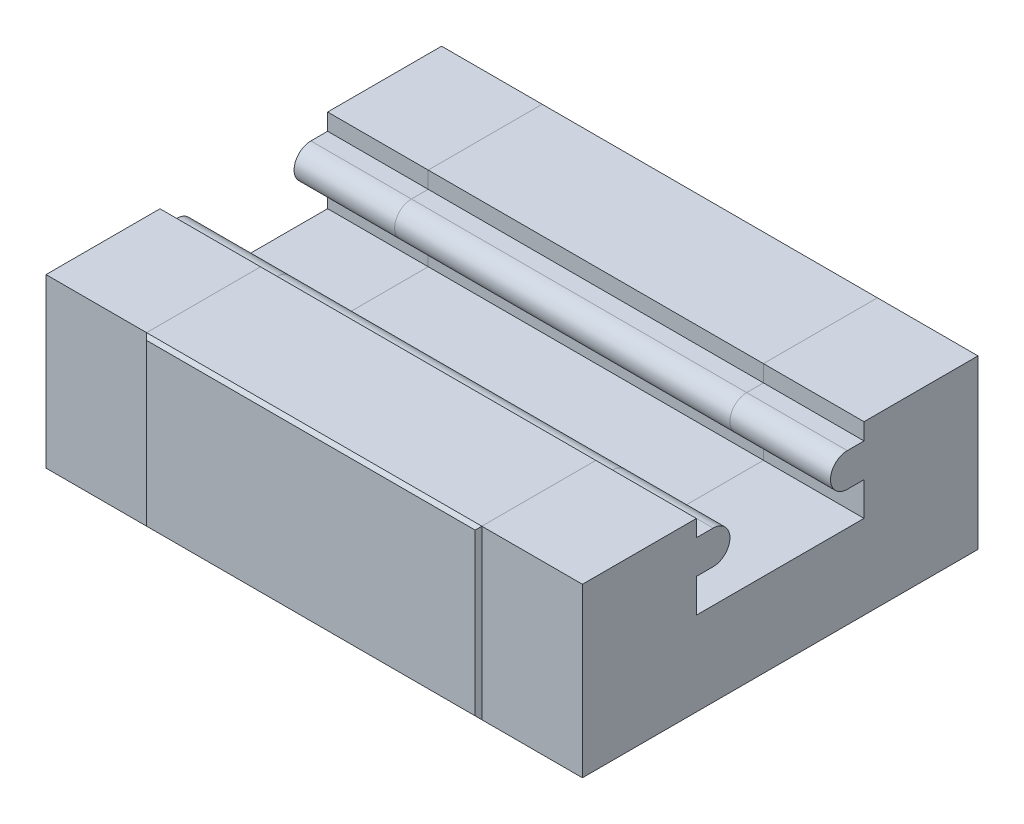
SolidWorks part; units mm, degrees
ref_plane "Front Plane" through (0, 0, 0) normal (0, 0, 1) x (1, 0, 0)
ref_plane "Top Plane" through (0, 0, 0) normal (0, 1, 0) x (1, 0, 0)
ref_plane "Right Plane" through (0, 0, 0) normal (1, 0, 0) x (0, 0, -1)
sketch "Sketch1" plane through (0, 0, 0) normal (1, 0, 0) x (0, 0, -1)
  line L1 (-7.62, -3.175) -> (7.62, -3.175)
  line L2 (-7.62, -3.175) -> (-7.62, 3.175)
  line L3 (-7.62, 3.175) -> (-3.175, 3.175)
  line L4 (7.62, -3.175) -> (7.62, 3.175)
  line L5 (-7.62, -3.175) -> (7.62, 3.175) construction
  line L6 (-7.62, 3.175) -> (7.62, -3.175) construction
  line L7 (-3.175, 3.175) -> (-3.175, 2.543)
  line L8 (-3.175, 0.003) -> (3.175, 0.003)
  line L9 (3.175, 0.003) -> (3.175, 1.273)
  line L10 (-3.175, 2.543) -> (-1.905, 2.543)
  line L11 (-1.905, 2.543) -> (-1.905, 1.273)
  line L12 (-1.905, 1.273) -> (-3.175, 1.273)
  line L13 (3.175, 2.543) -> (1.905, 2.543)
  line L14 (1.905, 2.543) -> (1.905, 1.273)
  line L15 (1.905, 1.273) -> (3.175, 1.273)
  line L16 (3.175, 3.175) -> (7.62, 3.175)
  line L17 (3.175, 2.543) -> (3.175, 3.175)
  line L18 (-3.175, 1.273) -> (-3.175, 0.003)
  point P0 (0, 0)
  point P17 (0, 0.003)
  dimension "D1" = 15.24
  dimension "D2" = 6.35
  dimension "D3" = 6.35
  dimension "D4" = 1.27
  dimension "D5" = 1.27
  dimension "D6" = 1.27
  dimension "D7" = 0.632
  dimension "D8" = 1.27
  dimension "D9" = 1.27
extrude "Boss-Extrude1" add sketch "Sketch1" along normal blind 12.7
fillet "Fillet1" 2 edges at (6.35, 2.543, -1.905) (6.35, 1.273, -1.905) type full round first side face at (6.35, 2.543, -2.54) second side face at (6.35, 1.273, -2.54) middle face at (6.35, 1.908, -1.905)
fillet "Fillet2" 2 edges at (6.35, 2.543, 1.905) (6.35, 1.273, 1.905) type full round first side face at (6.35, 2.543, 2.54) second side face at (6.35, 1.273, 2.54) middle face at (6.35, 1.908, 1.905)
chamfer "Chamfer1" distance 0.127 angle 45 8 edges at (6.35, -3.175, -7.62) (12.7, 0, -7.62) (6.35, 3.175, -7.62) (0, 0, -7.62) (6.35, 3.175, 7.62) (12.7, 0, 7.62) (6.35, -3.175, 7.62) (0, 0, 7.62)
sketch "Sketch2" plane through (12.7, 0, 0) normal (1, 0, 0) x (0, 0, -1)
  line L14 (-7.493, -3.175) -> (7.493, -3.175)
  line L15 (7.493, -3.175) -> (7.493, 3.175)
  line L16 (7.493, 3.175) -> (3.175, 3.175)
  line L17 (3.175, 3.175) -> (3.175, 2.543)
  line L18 (3.175, 2.543) -> (2.54, 2.543)
  line L19 (2.54, 1.273) -> (3.175, 1.273)
  line L20 (3.175, 1.273) -> (3.175, 0.003)
  line L21 (3.175, 0.003) -> (-3.175, 0.003)
  line L22 (-3.175, 0.003) -> (-3.175, 1.273)
  line L23 (-3.175, 1.273) -> (-2.54, 1.273)
  line L24 (-2.54, 2.543) -> (-3.175, 2.543)
  line L25 (-3.175, 2.543) -> (-3.175, 3.175)
  line L26 (-3.175, 3.175) -> (-7.493, 3.175)
  line L27 (-7.493, 3.175) -> (-7.493, -3.175)
  line L28 (-7.493, -3.175) -> (7.493, -3.175)
  line L29 (7.493, -3.175) -> (7.493, 3.175)
  line L30 (7.493, 3.175) -> (3.175, 3.175)
  line L31 (3.175, 3.175) -> (3.175, 2.543)
  line L32 (3.175, 2.543) -> (2.54, 2.543)
  line L33 (2.54, 1.273) -> (3.175, 1.273)
  line L34 (3.175, 1.273) -> (3.175, 0.003)
  line L35 (3.175, 0.003) -> (-3.175, 0.003)
  line L36 (-3.175, 0.003) -> (-3.175, 1.273)
  line L37 (-3.175, 1.273) -> (-2.54, 1.273)
  line L38 (-2.54, 2.543) -> (-3.175, 2.543)
  line L39 (-3.175, 2.543) -> (-3.175, 3.175)
  line L40 (-3.175, 3.175) -> (-7.493, 3.175)
  line L41 (-7.493, 3.175) -> (-7.493, -3.175)
  arc A2 (2.54, 2.543) -> (2.54, 1.273) centre (2.54, 1.908) ccw
  arc A3 (-2.54, 1.273) -> (-2.54, 2.543) centre (-2.54, 1.908) ccw
  arc A4 (2.54, 2.543) -> (2.54, 1.273) centre (2.54, 1.908) ccw
  arc A5 (-2.54, 1.273) -> (-2.54, 2.543) centre (-2.54, 1.908) ccw
  dimension "D1" = 0
extrude "Boss-Extrude2" add sketch "Sketch2" along normal blind 3.81 separate body
sketch "Sketch3" plane through (0, 0, 0) normal (-1, 0, 0) x (0, 0, 1)
  line L14 (-3.175, 3.175) -> (-7.493, 3.175)
  line L15 (-7.493, 3.175) -> (-7.493, -3.175)
  line L16 (-7.493, -3.175) -> (7.493, -3.175)
  line L17 (7.493, -3.175) -> (7.493, 3.175)
  line L18 (7.493, 3.175) -> (3.175, 3.175)
  line L19 (3.175, 3.175) -> (3.175, 2.543)
  line L20 (3.175, 2.543) -> (2.54, 2.543)
  line L21 (2.54, 1.273) -> (3.175, 1.273)
  line L22 (3.175, 1.273) -> (3.175, 0.003)
  line L23 (3.175, 0.003) -> (-3.175, 0.003)
  line L24 (-3.175, 0.003) -> (-3.175, 1.273)
  line L25 (-3.175, 1.273) -> (-2.54, 1.273)
  line L26 (-2.54, 2.543) -> (-3.175, 2.543)
  line L27 (-3.175, 2.543) -> (-3.175, 3.175)
  line L28 (-3.175, 3.175) -> (-7.493, 3.175)
  line L29 (-7.493, 3.175) -> (-7.493, -3.175)
  line L30 (-7.493, -3.175) -> (7.493, -3.175)
  line L31 (7.493, -3.175) -> (7.493, 3.175)
  line L32 (7.493, 3.175) -> (3.175, 3.175)
  line L33 (3.175, 3.175) -> (3.175, 2.543)
  line L34 (3.175, 2.543) -> (2.54, 2.543)
  line L35 (2.54, 1.273) -> (3.175, 1.273)
  line L36 (3.175, 1.273) -> (3.175, 0.003)
  line L37 (3.175, 0.003) -> (-3.175, 0.003)
  line L38 (-3.175, 0.003) -> (-3.175, 1.273)
  line L39 (-3.175, 1.273) -> (-2.54, 1.273)
  line L40 (-2.54, 2.543) -> (-3.175, 2.543)
  line L41 (-3.175, 2.543) -> (-3.175, 3.175)
  arc A2 (2.54, 2.543) -> (2.54, 1.273) centre (2.54, 1.908) ccw
  arc A3 (-2.54, 1.273) -> (-2.54, 2.543) centre (-2.54, 1.908) ccw
  arc A4 (2.54, 2.543) -> (2.54, 1.273) centre (2.54, 1.908) ccw
  arc A5 (-2.54, 1.273) -> (-2.54, 2.543) centre (-2.54, 1.908) ccw
  dimension "D1" = 0
extrude "Boss-Extrude3" add sketch "Sketch3" along normal blind 3.81 separate body
